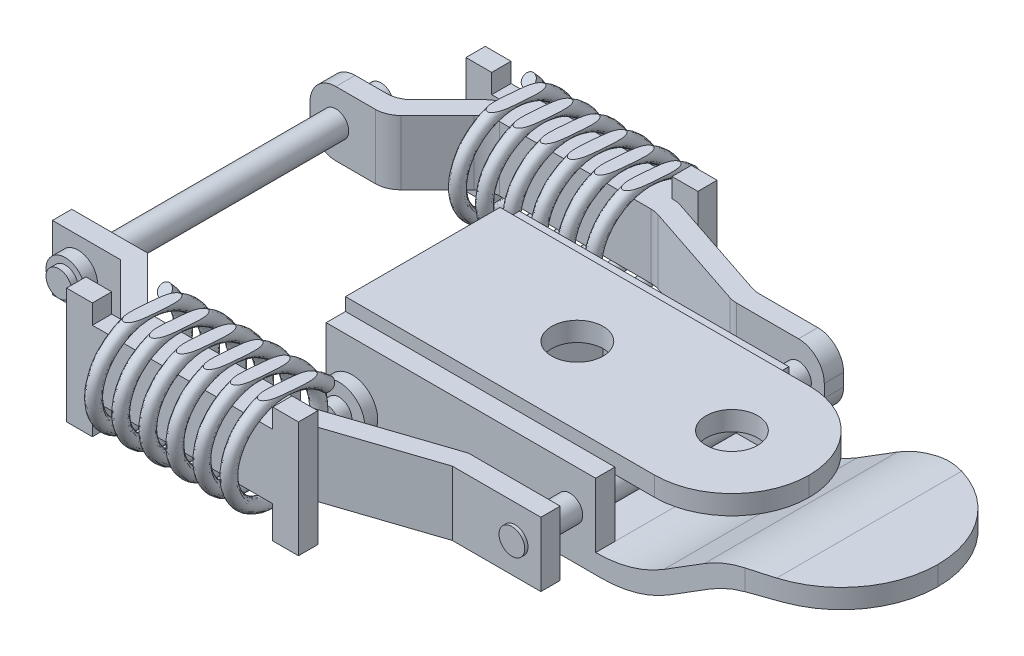
SolidWorks part; units mm, degrees
material "AISI 304"
ref_plane "前视基准面" through (0, 0, 0) normal (0, 0, 1) x (1, 0, 0)
ref_plane "上视基准面" through (0, 0, 0) normal (0, 1, 0) x (1, 0, 0)
ref_plane "右视基准面" through (0, 0, 0) normal (1, 0, 0) x (0, 0, -1)
sketch "草图1" plane through (0, 0, 0) normal (0, 0, 1) x (1, 0, 0)
  line L0 (0, 0) -> (24, 0) construction
  line L1 (24, 0) -> (32, 5) construction
  line L2 (32, 5) -> (40, 5) construction
  line L3 (0, -0.75) -> (24.2151, -0.75)
  line L4 (24.2151, -0.75) -> (32.2151, 4.25)
  line L5 (32.2151, 4.25) -> (40, 4.25)
  line L6 (0, 0.75) -> (23.7849, 0.75)
  line L7 (23.7849, 0.75) -> (31.7849, 5.75)
  line L8 (31.7849, 5.75) -> (40, 5.75)
  line L9 (0, 0.75) -> (0, -0.75)
  line L10 (40, 5.75) -> (40, 4.25)
  dimension "D1" = 24
  dimension "D2" = 16
  dimension "D3" = 5
  dimension "D4" = 8
  dimension "D5" = 0.75
  dimension "D6" = 0.75
extrude "凸台-拉伸1" add sketch "草图1" along normal mid plane 15
fillet "圆角1" radius 10 4 edges at (24.2151, -0.75, 0) (32.2151, 4.25, 0) (31.7849, 5.75, 0) (23.7849, 0.75, 0)
fillet "圆角2" radius 7.5 2 edges at (40, 5, -7.5) (40, 5, 7.5)
sketch "草图2" plane through (0, 0.75, 0) normal (0, 1, 0) x (1, 0, 0)
  line L0 (20.9169, -7.5) -> (20.9169, 7.5) construction
  line L1 (0, 7.5) -> (20.9169, 7.5)
  line L2 (0, 7.5) -> (0, 6)
  line L3 (0, 6) -> (20.9169, 6)
  line L4 (20.9169, 7.5) -> (20.9169, 6)
  line L5 (0, -7.5) -> (0, 7.5) construction
  line L6 (20.9169, -7.5) -> (0, -7.5)
  line L7 (20.9169, -7.5) -> (20.9169, -6)
  line L8 (20.9169, -6) -> (0, -6)
  line L9 (0, -7.5) -> (0, -6)
  line L10 (0, 0) -> (50000, 0) construction
  dimension "D1" = 1.5
extrude "凸台-拉伸2" add sketch "草图2" along normal blind 5
sketch "草图7" plane through (0, 0, 0) normal (-1, 0, 0) x (0, 0, 1)
  line L0 (0, 0) -> (50000, 0) construction
  line L1 (0, 0) -> (0, 50000) construction
  line L2 (6, 0.75) -> (-6, 0.75) construction
  line L3 (-6, 0.75) -> (6, 0.75)
  line L4 (-6, 0.75) -> (-6, 6.75)
  line L5 (-6, 6.75) -> (6, 6.75)
  line L6 (6, 0.75) -> (6, 6.75)
  line L7 (-6, 0.75) -> (6, 6.75) construction
  line L8 (-6, 6.75) -> (6, 0.75) construction
  line L9 (-6, 5.75) -> (-6, 0.75) construction
  point P5 (0, 3.75)
  dimension "D1" = 6
extrude "凸台-拉伸3" add sketch "草图7" against normal blind 8 separate body
sketch "草图4" plane through (0, -0.75, 0) normal (0, -1, 0) x (1, 0, 0)
  line L0 (0, 0) -> (-50000, 0) construction
  line L1 (0, 7.5) -> (0, -7.5) construction
  line L2 (0, 6) -> (4, 6)
  line L3 (0, 6) -> (0, 4.5)
  line L4 (0, 4.5) -> (4, 4.5)
  line L5 (4, 6) -> (4, 4.5)
  line L6 (0, 7.5) -> (21.3471, 7.5) construction
  line L7 (0, -4.5) -> (4, -4.5)
  line L8 (0, -4.5) -> (0, -6)
  line L9 (0, -6) -> (4, -6)
  line L10 (4, -4.5) -> (4, -6)
  line L11 (0, -7.5) -> (21.3471, -7.5) construction
  dimension "D1" = 1.5
  dimension "D2" = 1.5
  dimension "D3" = 4
  dimension "D4" = 1.5
  dimension "D5" = 1.5
extrude "切除-拉伸1" cut sketch "草图4" against normal blind 4
sketch "草图5" plane through (0, 0, -7.5) normal (0, 0, -1) x (-1, 0, 0)
  line L0 (0, 5.75) -> (0, -0.75) construction
  line L1 (0, -0.75) -> (-21.3471, -0.75) construction
  circle A0 centre (-2, 1.25) radius 1
  dimension "D1" = 2
  dimension "D2" = 2
  dimension "D3" = 2
extrude "切除-拉伸2" cut sketch "草图5" against normal blind 21.5
sketch "草图10" plane through (0, 0, -4.5) normal (0, 0, -1) x (-1, 0, 0)
  circle A0 centre (-2, 1.25) radius 1.95
  circle A1 centre (-2, 1.25) radius 1
  dimension "D1" = 2
  dimension "D2" = 3.9
extrude "凸台-拉伸8" add sketch "草图10" along normal blind 1.5
sketch "草图11" plane through (0, 0, 4.5) normal (0, 0, 1) x (1, 0, 0)
  circle A0 centre (2, 1.25) radius 1
  circle A1 centre (2, 1.25) radius 1.95
  dimension "D1" = 2
  dimension "D2" = 3.9
extrude "凸台-拉伸9" add sketch "草图11" along normal blind 1.5
sketch "草图13" plane through (8, 0, 0) normal (1, 0, 0) x (0, 0, -1)
  line L0 (6, 6.75) -> (6, 0.75) construction
  line L1 (-6, 6.75) -> (6, 6.75)
  line L2 (-6, 6.75) -> (-6, 5.25)
  line L3 (-6, 5.25) -> (6, 5.25)
  line L4 (6, 6.75) -> (6, 5.25)
  dimension "D1" = 1.5
extrude "凸台-拉伸11" add sketch "草图13" along normal blind 22
fillet "圆角4" radius 6 4 edges at (30, 6, 6) (30, 5.25, 0) (30, 6, -6) (30, 6.75, 0)
sketch "草图14" plane through (0, 6.75, 0) normal (0, 1, 0) x (1, 0, 0)
  line L0 (12, 0) -> (24, 0) construction
  line L1 (0, 0) -> (-50000, 0) construction
  line L2 (0, -6) -> (0, 6) construction
  circle A0 centre (24, 0) radius 2
  circle A1 centre (12, 0) radius 2
  arc A2 (30, 0) -> (24, 6) centre (24, 0) ccw construction
  point P8 (0, 0)
  dimension "D1" = 12
  dimension "D2" = 4
extrude "切除-拉伸7" cut sketch "草图14" against normal blind 2
sketch "草图15" plane through (0, 0, 7.5) normal (0, 0, 1) x (1, 0, 0)
  circle A0 centre (2, 1.25) radius 1
  dimension "D1" = 2
extrude "切除-拉伸8" cut sketch "草图15" against normal blind 22
sketch "草图16" plane through (0, 0, 7.5) normal (0, 0, 1) x (1, 0, 0)
  circle A0 centre (2, 1.25) radius 2
  dimension "D1" = 4
extrude "凸台-拉伸12" add sketch "草图16" along normal blind 1
sketch "草图17" plane through (0, 0, 8.5) normal (0, 0, 1) x (1, 0, 0)
  circle A0 centre (2, 1.25) radius 1
  dimension "D1" = 2
extrude "凸台-拉伸13" add sketch "草图17" against normal blind 18 and the other way blind 1
mirror "镜向2" about plane through (0, 0, 0) normal (0, 0, 1) of "凸台-拉伸12"
sketch "草图18" plane through (0, 0, 7.5) normal (0, 0, 1) x (1, 0, 0)
  line L0 (20.9169, 5.75) -> (20.9169, 0.75) construction
  line L1 (2, -0.75) -> (21.3471, -0.75) construction
  circle A0 centre (18.9169, 2.75) radius 1
  dimension "D1" = 2
  dimension "D2" = 2
  dimension "D3" = 3.5
extrude "切除-拉伸9" cut sketch "草图18" against normal blind 18
sketch "草图19" plane through (0, 0, 0) normal (0, 0, 1) x (1, 0, 0)
  line L0 (24, 6.75) -> (0, 6.75) construction
  line L1 (2, -0.75) -> (21.3471, -0.75) construction
  circle A0 centre (18.9169, 2.75) radius 1
  dimension "D1" = 2
extrude "凸台-拉伸14" add sketch "草图19" along normal mid plane 24
ref_plane "基准面2" through (0, 2.75, 0) normal (0, 1, 0) x (1, 0, 0)
sketch "草图20" plane through (0, 2.75, 0) normal (0, 1, 0) x (1, 0, 0)
  line L0 (18.9169, 11) -> (13.9169, 11) construction
  line L1 (13.9169, 11) -> (4.9169, 14) construction
  line L2 (4.9169, 14) -> (-8.4164, 14) construction
  line L3 (-8.4164, 14) -> (-12.4164, 10) construction
  line L4 (-12.4164, 10) -> (-18, 10) construction
  line L5 (19.9169, 12) -> (17.9169, 12) construction
  line L6 (18.9169, 12) -> (18.9169, 50012) construction
  line L8 (0, -6) -> (0, 6) construction
  line L9 (18.9169, 11.75) -> (14.0386, 11.75)
  line L10 (14.0386, 11.75) -> (5.0386, 14.75)
  line L11 (5.0386, 14.75) -> (-8.7271, 14.75)
  line L12 (-8.7271, 14.75) -> (-12.7271, 10.75)
  line L13 (-12.7271, 10.75) -> (-18, 10.75)
  line L14 (18.9169, 10.25) -> (13.7952, 10.25)
  line L15 (13.7952, 10.25) -> (4.7952, 13.25)
  line L16 (4.7952, 13.25) -> (-8.1057, 13.25)
  line L17 (-8.1057, 13.25) -> (-12.1057, 9.25)
  line L18 (-12.1057, 9.25) -> (-18, 9.25)
  line L19 (-18, 10.75) -> (-18, 9.25)
  line L21 (18.9169, 11.75) -> (20.9169, 11.75)
  line L22 (20.9169, 11.75) -> (20.9169, 10.25)
  line L23 (20.9169, 10.25) -> (18.9169, 10.25)
  point P12 (18.9169, 12)
  dimension "D1" = 1
  dimension "D2" = 13.3333
  dimension "D3" = 14
  dimension "D4" = 9
  dimension "D5" = 5
  dimension "D6" = 10
  dimension "D7" = 4
  dimension "D8" = 18
  dimension "D11" = 2
  dimension "D9" = 0.75
  dimension "D10" = 0.75
extrude "凸台-拉伸15" add sketch "草图20" along normal mid plane 5
fillet "圆角5" radius 2 2 edges at (20.9169, 0.25, -11) (20.9169, 5.25, -11)
fillet "圆角6" radius 2 8 edges at (-12.1057, 2.75, -9.25) (-12.7271, 2.75, -10.75) (-8.7271, 2.75, -14.75) (-8.1057, 2.75, -13.25) (13.7952, 2.75, -10.25) (4.7952, 2.75, -13.25) (5.0386, 2.75, -14.75) (14.0386, 2.75, -11.75)
fillet "圆角7" radius 2 2 edges at (-18, 5.25, -10) (-18, 0.25, -10)
ref_plane "基准面3" through (4, 0, 0) normal (-1, 0, 0) x (0, 0, 1)
sketch "草图22" plane through (4, 0, 0) normal (-1, 0, 0) x (0, 0, 1)
  line L1 (-14.1642, 5.25) -> (-14.75, 5.25) construction
  line L2 (-14.75, 0.25) -> (-14.75, 5.25) construction
  circle A0 centre (-14, 2.75) radius 4
  dimension "D3" = 8
  dimension "D1" = 2.5
  dimension "D2" = 0.75
curve "螺旋线/涡状线1" pitch 2.1 height 12.6 turns 6
sweep "扫描1" add path "螺旋线/涡状线1" circular profile diameter 1 parameters "D3"=1
sketch "草图29" plane through (0, 0, -9.25) normal (0, 0, 1) x (1, 0, 0)
  line L0 (-16, 5.25) -> (-12.9342, 5.25) construction
  line L1 (-18, 3.25) -> (-18, 2.25) construction
  circle A0 centre (-16, 2.75) radius 1
  dimension "D1" = 2
  dimension "D2" = 2.5
  dimension "D3" = 2
extrude "切除-拉伸10" cut sketch "草图29" against normal blind 5
sketch "草图30" plane through (0, 0, -10.75) normal (0, 0, -1) x (-1, 0, 0)
  circle A0 centre (16, 2.75) radius 1.5
  circle A1 centre (16, 2.75) radius 1
  dimension "D1" = 3
  dimension "D2" = 2
extrude "凸台-拉伸16" add sketch "草图30" along normal blind 1
sketch "草图31" plane through (0, 0, -11.75) normal (0, 0, -1) x (-1, 0, 0)
  circle A0 centre (16, 2.75) radius 1
  dimension "D1" = 2
extrude "凸台-拉伸17" add sketch "草图31" along normal blind 1 and the other way blind 24
sketch "草图32" plane through (0, 0, -14.75) normal (0, 0, -1) x (-1, 0, 0)
  line L0 (-13.7307, 5.25) -> (-5.3465, 5.25) construction
  line L1 (-6.6, 5.25) -> (11.4, 5.25)
  line L2 (-6.6, 5.25) -> (-6.6, 0.25)
  line L3 (-6.6, 0.25) -> (11.4, 0.25)
  line L4 (11.4, 5.25) -> (11.4, 0.25)
  line L6 (-6.6, 5.25) -> (-6.6, 7.75)
  line L7 (-6.6, 7.75) -> (-4.6, 7.75)
  line L8 (-4.6, 7.75) -> (-4.6, 5.25)
  line L9 (-6.6, 0.25) -> (-6.6, -2.25)
  line L10 (-6.6, -2.25) -> (-4.6, -2.25)
  line L11 (-4.6, -2.25) -> (-4.6, 0.25)
  line L12 (11.4, 5.25) -> (11.4, 7.75)
  line L13 (11.4, 7.75) -> (9.4, 7.75)
  line L14 (9.4, 7.75) -> (9.4, 5.25)
  line L15 (11.4, 0.25) -> (11.4, -2.25)
  line L16 (11.4, -2.25) -> (9.4, -2.25)
  line L17 (9.4, -2.25) -> (9.4, 0.25)
  line M13 (-4.7141, 0.25) -> (7.8986, 0.25)
  line M14 (7.8986, 0.25) -> (7.8986, 5.25)
  line M15 (7.8986, 5.25) -> (-4.7141, 5.25)
  line M16 (-4.7141, 5.25) -> (-4.7141, 0.25)
  dimension "D1" = 18
  dimension "D2" = 2
  dimension "D3" = 2
  dimension "D4" = 2.5
  dimension "D5" = 2.5
  dimension "D6" = 2
  dimension "D7" = 2
  dimension "D8" = 5
  dimension "D9" = 2.5
  dimension "D10" = 2.5
  dimension "D11" = 6.6
extrude "凸台-拉伸18" add sketch "草图32" along normal blind 1.5 contours L8 L7 L6 L1 | L2 L3 L1 M16 | M16 M13 M14 M15 | L4 L1 L3 M14 | L13 L14 L1 L12 | L17 L16 L15 L3 | L10 L11 L3 L9
mirror "镜向14" about plane through (0, 0, 0) normal (0, 0, 1) of "凸台-拉伸16", "凸台-拉伸18", "凸台-拉伸15"
sketch "草图43" plane through (4, 0, 0) normal (-1, 0, 0) x (0, 0, 1)
  line L1 (14.75, 5.25) -> (10.75, 5.25) construction
  line L4 (14.75, 5.25) -> (14.75, 0.25) construction
  circle A0 centre (14.25, 2.75) radius 4
  dimension "D1" = 8
  dimension "D2" = 2.5
  dimension "D3" = 0.5
curve "螺旋线/涡状线2" pitch 2.1 height 12.6 turns 6
sweep "扫描2" add path "螺旋线/涡状线2" circular profile diameter 1 parameters "D3"=1
sketch "草图45" plane through (0, 6.75, 0) normal (0, 1, 0) x (1, 0, 0)
  line L1 (-47.6945, -22.4538) -> (47.6945, -22.4538)
  line L2 (-47.6945, -22.4538) -> (-47.6945, 22.4538)
  line L3 (-47.6945, 22.4538) -> (47.6945, 22.4538)
  line L4 (47.6945, -22.4538) -> (47.6945, 22.4538)
  line L5 (0, 22.4538) -> (0, -22.4538) construction
  line L6 (-47.6945, 0) -> (47.6945, 0) construction
  point P0 (0, 0)
extrude "切除-拉伸11" cut sketch "草图45" along normal blind 10
